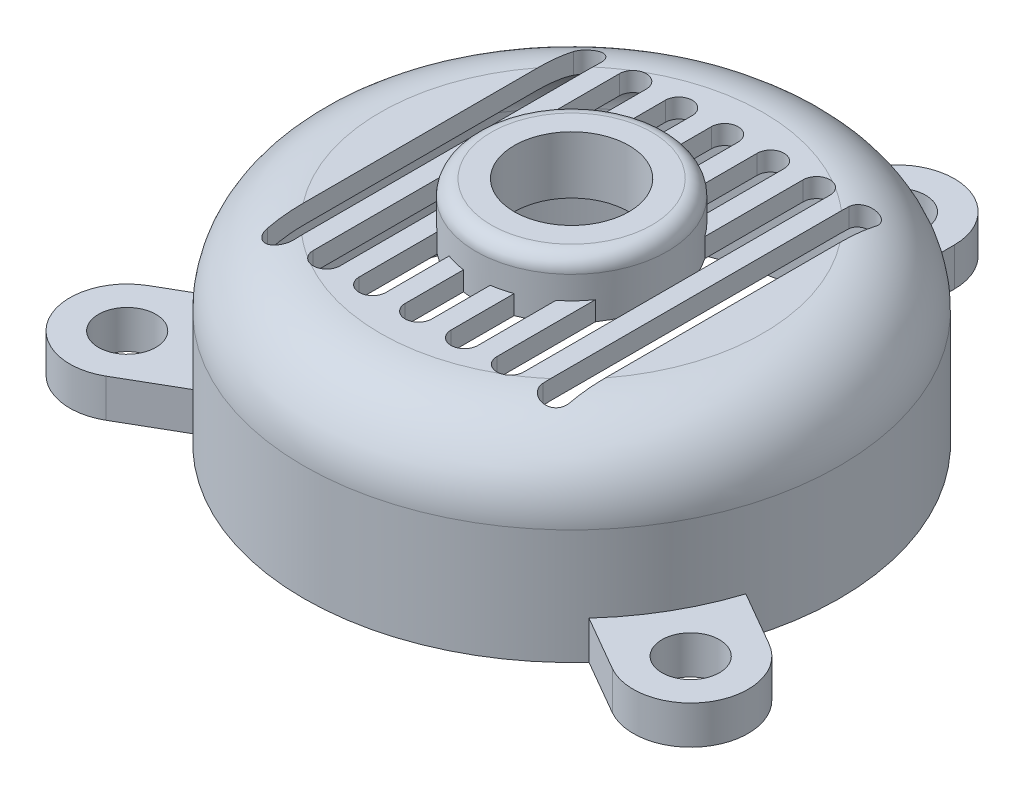
SolidWorks part; units mm, degrees
note: The reader was unsure of these and kept them because the rebuilt part matched: shared geometry of "Sketch1<3>", "Sketch4<2>".
ref_plane "Front Plane" through (0, 0, 0) normal (0, 0, 1) x (1, 0, 0)
ref_plane "Top Plane" through (0, 0, 0) normal (0, 1, 0) x (1, 0, 0)
ref_plane "Right Plane" through (0, 0, 0) normal (1, 0, 0) x (0, 0, -1)
sketch "Sketch1" plane through (0, 0, 0) normal (0, 1, 0) x (1, 0, 0)
  line L0 (-19.05, 107.95) -> (-19.05, 86.8349)
  line L1 (19.05, 107.95) -> (19.05, 86.8349)
  line L2 (103.0124, -37.4772) -> (84.7263, -26.9197)
  line L3 (83.9624, -70.4728) -> (65.6763, -59.9153)
  line L4 (-83.9624, -70.4728) -> (-65.6763, -59.9153)
  line L5 (-103.0124, -37.4772) -> (-84.7263, -26.9197)
  circle A0 centre (0, 0) radius 88.9
  circle A1 centre (0, 0) radius 107.95 construction
  circle A2 centre (0, 107.95) radius 9.525
  arc A3 (18.9757, 106.2691) -> (-18.9757, 106.2691) centre (0, 107.95) ccw
  arc A4 (82.5439, -69.568) -> (101.5196, -36.7011) centre (93.4874, -53.975) ccw
  circle A5 centre (93.4874, -53.975) radius 9.525
  arc A6 (-101.5196, -36.7011) -> (-82.5439, -69.568) centre (-93.4874, -53.975) ccw
  circle A7 centre (-93.4874, -53.975) radius 9.525
  point P31 (0, 0)
  dimension "D1" = 177.8
  dimension "D2" = 215.9
  dimension "D3" = 19.05
  dimension "D4" = 38.1
  dimension "D5" = 3
extrude "Boss-Extrude1" add sketch "Sketch1" along normal blind 63.5 contours A0
fillet "Fillet1" radius 25.4 1 edges at (0, 63.5, 88.9)
shell "Shell1" thickness 6.35
extrude "Boss-Extrude2" add sketch "Sketch1<3>" along normal blind 12.7
sketch "Sketch1<3>" plane through (0, 0, 0) normal (0, 1, 0) x (1, 0, 0) same geometry as "Sketch1"
sketch "Sketch3" plane through (0, 63.5, 0) normal (0, 1, 0) x (1, 0, 0)
  line L0 (-34.925, 50.8) -> (-34.925, -50.8)
  line L1 (-50.165, 50.8) -> (-41.275, 50.8) construction
  line L2 (-50.165, 50.8) -> (-50.165, -50.8)
  line L3 (-50.165, -50.8) -> (-41.275, -50.8) construction
  line L4 (-41.275, 50.8) -> (-41.275, -50.8)
  line L5 (-26.035, 50.8) -> (-26.035, -50.8)
  line L6 (-19.685, 50.8) -> (-19.685, -50.8)
  line L7 (-10.795, 50.8) -> (-10.795, -50.8)
  line L8 (-4.445, 50.8) -> (-4.445, -50.8)
  line L9 (4.445, 50.8) -> (4.445, -50.8)
  line L10 (10.795, 50.8) -> (10.795, -50.8)
  line L11 (19.685, 50.8) -> (19.685, -50.8)
  line L12 (26.035, 50.8) -> (26.035, -50.8)
  line L13 (34.925, 50.8) -> (34.925, -50.8)
  line L14 (41.275, 50.8) -> (41.275, -50.8)
  line L15 (50.165, 50.8) -> (50.165, -50.8)
  arc A0 (-50.165, 50.8) -> (-41.275, 50.8) centre (-45.72, 50.8) cw
  arc A1 (-50.165, -50.8) -> (-41.275, -50.8) centre (-45.72, -50.8) ccw
  arc A2 (-34.925, 50.8) -> (-26.035, 50.8) centre (-30.48, 50.8) cw
  arc A3 (-34.925, -50.8) -> (-26.035, -50.8) centre (-30.48, -50.8) ccw
  arc A4 (-19.685, 50.8) -> (-10.795, 50.8) centre (-15.24, 50.8) cw
  arc A5 (-19.685, -50.8) -> (-10.795, -50.8) centre (-15.24, -50.8) ccw
  arc A6 (-4.445, 50.8) -> (4.445, 50.8) centre (0, 50.8) cw
  arc A7 (-4.445, -50.8) -> (4.445, -50.8) centre (0, -50.8) ccw
  arc A8 (10.795, 50.8) -> (19.685, 50.8) centre (15.24, 50.8) cw
  arc A9 (10.795, -50.8) -> (19.685, -50.8) centre (15.24, -50.8) ccw
  arc A10 (26.035, 50.8) -> (34.925, 50.8) centre (30.48, 50.8) cw
  arc A11 (26.035, -50.8) -> (34.925, -50.8) centre (30.48, -50.8) ccw
  arc A12 (41.275, 50.8) -> (50.165, 50.8) centre (45.72, 50.8) cw
  arc A13 (41.275, -50.8) -> (50.165, -50.8) centre (45.72, -50.8) ccw
  point P4 (-41.275, 0)
  dimension "D4" = 7
  dimension "D1" = 101.6
  dimension "D2" = 45.72
  dimension "D3" = 8.89
  dimension "D5" = 15.24
extrude "Cut-Extrude1" cut sketch "Sketch3" against normal up to next
sketch "Sketch4" plane through (0, 63.5, 0) normal (0, 1, 0) x (1, 0, 0)
  circle A0 centre (0, 0) radius 19.05
  circle A1 centre (0, 0) radius 31.75
  dimension "D1" = 38.1
  dimension "D2" = 63.5
extrude "Boss-Extrude3" add sketch "Sketch4" along normal blind 12.7 and the other way blind 6.35
fillet "Fillet2" radius 5.08 1 edges at (0, 76.2, 31.75)
extrude "Cut-Extrude2" cut sketch "Sketch4<2>" against normal up to next contours A0
sketch "Sketch4<2>" plane through (0, 63.5, 0) normal (0, 1, 0) x (1, 0, 0) same geometry as "Sketch4"
